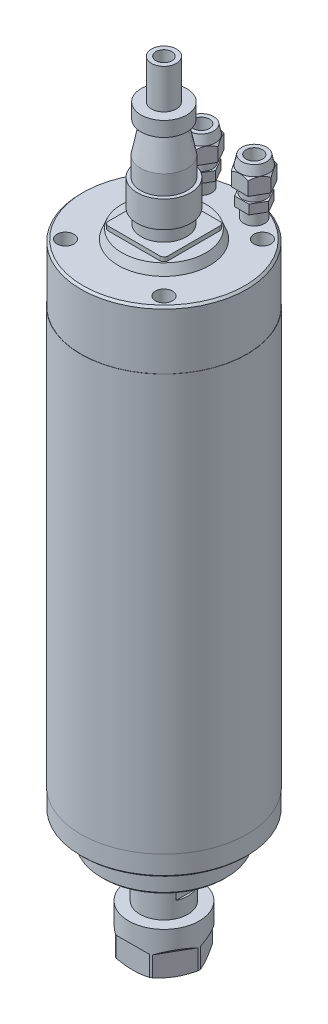
SolidWorks part; units mm, degrees
material "Plain Carbon Steel"
ref_plane "Front Plane" through (0, 0, 0) normal (0, 0, 1) x (1, 0, 0)
ref_plane "Top Plane" through (0, 0, 0) normal (0, 1, 0) x (1, 0, 0)
ref_plane "Right Plane" through (0, 0, 0) normal (1, 0, 0) x (0, 0, -1)
ref_axis "Axis1" through (0, 160.005, 0) along (0, -1, 0)
sketch "Sketch1" plane through (0, 0, 0) normal (1, 0, 0) x (0, 0, -1)
  line L0 (0, 128.3) -> (0, -128.3)
  line L1 (0, 128.3) -> (-39.9, 128.3)
  line L2 (-39.9, 128.3) -> (-39.9, 100.3)
  line L3 (-39.9, 100.3) -> (-40, 100.3)
  line L4 (-40, 100.3) -> (-40, -99.7)
  line L5 (-40, -99.7) -> (-39.9, -99.7)
  line L6 (-39.9, -99.7) -> (-39.9, -109.7)
  line L7 (-39.9, -109.7) -> (-30, -109.7)
  line L8 (-30, -109.7) -> (-30, -123.7)
  line L9 (-30, -123.7) -> (-24.1, -123.7)
  line L10 (-24.1, -123.7) -> (-24.1, -128.3)
  line L11 (-24.1, -128.3) -> (0, -128.3)
  dimension "D1" = 40
  dimension "D2" = 39.9
  dimension "D3" = 39.9
  dimension "D4" = 28
  dimension "D5" = 200
  dimension "D6" = 10
  dimension "D7" = 14
  dimension "D8" = 30
  dimension "D9" = 4.6
  dimension "D10" = 24.1
revolve "Revolve1" add sketch "Sketch1" angle 360 about L0
chamfer "Chamfer2" distance 7 distance2 1.5 1 edges at (0, -128.3, 24.1) first distance on face at (0, -128.3, 24.1)
sketch "Sketch2" plane through (0, -128.3, 0) normal (0, -1, 0) x (1, 0, 0)
  circle A0 centre (0, 0) radius 11.5
  dimension "D1" = 23
extrude "Boss-Extrude1" add sketch "Sketch2" along normal blind 19
chamfer "Chamfer1" distance 1 angle 45 3 edges at (0, 128.3, 39.9) (0, -109.7, 39.9) (0, -123.7, 30)
sketch "Sketch3" plane through (0, -147.3, 0) normal (0, -1, 0) x (1, 0, 0)
  circle A0 centre (0, 0) radius 17
  dimension "D1" = 34
extrude "Boss-Extrude2" add sketch "Sketch3" along normal blind 22.5
ref_plane "Plane1" through (21.67, 0, 0) normal (1, 0, 0) x (0, 0, -1)
chamfer "Chamfer3" distance 2 distance2 4 1 edges at (0, -169.8, -17) first distance on face at (0, -169.8, -17)
sketch "Sketch7" plane through (0, 0, 0) normal (1, 0, 0) x (0, 0, -1)
  line L0 (0, -169.8) -> (0, -147.3) construction
  line L1 (-29.8933, -143.3067) -> (-15, -158.2)
  line L2 (-29.8933, -143.3067) -> (-29.8933, -177.0813)
  line L3 (-29.8933, -177.0813) -> (-15, -177.0813)
  line L4 (-15, -158.2) -> (-15, -177.0813)
  line L5 (-17, -169.8) -> (17, -169.8) construction
  line L6 (17, -147.3) -> (-17, -147.3) construction
  dimension "D1" = 45
  dimension "D2" = 15
  dimension "D3" = 11.6
extrude "Cut-Extrude1" cut sketch "Sketch7" against normal through all both and the other way through all
pattern_circular "CirPattern1" count 6 over 360 about axis through (0, 160.005, 0) along (0, -1, 0) of "Cut-Extrude1"
sketch "Sketch9" plane through (0, -169.8, 0) normal (0, -1, 0) x (1, 0, 0)
  circle A0 centre (0, 0) radius 7.7
  dimension "D1" = 15.4
extrude "Cut-Extrude2" cut sketch "Sketch9" against normal blind 10
sketch "Sketch10" plane through (0, 128.3, 0) normal (0, 1, 0) x (1, 0, 0)
  circle A0 centre (0, 0) radius 22
  dimension "D1" = 44
extrude "Boss-Extrude3" add sketch "Sketch10" along normal blind 4.4 draft 22
sketch "Sketch11" plane through (0, 128.3, 0) normal (0, 1, 0) x (1, 0, 0)
  line L0 (-23.6881, 23.6881) -> (-26.5872, 26.5872) construction
  line L1 (23.6881, -23.6881) -> (-23.6881, -23.6881) construction
  line L2 (23.6881, -23.6881) -> (23.6881, 23.6881) construction
  line L3 (23.6881, 23.6881) -> (-23.6881, 23.6881) construction
  line L4 (-23.6881, -23.6881) -> (-23.6881, 23.6881) construction
  line L5 (23.6881, -23.6881) -> (-23.6881, 23.6881) construction
  line L6 (23.6881, 23.6881) -> (-23.6881, -23.6881) construction
  line L7 (-26.5872, 26.5872) -> (-28.2843, 28.2843) construction
  circle A0 centre (-23.6881, 23.6881) radius 4.1
  circle A1 centre (23.6881, 23.6881) radius 4.1
  circle A2 centre (23.6881, -23.6881) radius 4.1
  circle A3 centre (-23.6881, -23.6881) radius 4.1
  circle A4 centre (0, 0) radius 40 construction
  point P0 (0, 0)
  dimension "D1" = 8.2
  dimension "D2" = 2.4
extrude "Cut-Extrude3" cut sketch "Sketch11" against normal blind 10
sketch "Sketch12" plane through (0, 128.3, 0) normal (0, 1, 0) x (1, 0, 0)
  line L0 (0, 0) -> (0, 30.7) construction
  line L1 (0, 30.7) -> (-12.75, 30.7) construction
  line L2 (-12.75, 30.7) -> (-17.75, 30.7) construction
  circle A0 centre (-12.75, 30.7) radius 5
  dimension "D1" = 10
  dimension "D2" = 17.75
  dimension "D3" = 30.7
extrude "Boss-Extrude4" add sketch "Sketch12" along normal blind 5.8
sketch "Sketch13" plane through (0, 134.1, 0) normal (0, 1, 0) x (1, 0, 0)
  line L1 (-19.6782, 30.7) -> (-16.2141, 24.7)
  line L2 (-16.2141, 24.7) -> (-9.2859, 24.7)
  line L3 (-9.2859, 24.7) -> (-5.8218, 30.7)
  line L4 (-5.8218, 30.7) -> (-9.2859, 36.7)
  line L5 (-9.2859, 36.7) -> (-16.2141, 36.7)
  line L6 (-16.2141, 36.7) -> (-19.6782, 30.7)
  circle A0 centre (-12.75, 30.7) radius 6 construction
  dimension "D1" = 12
extrude "Boss-Extrude5" add sketch "Sketch13" along normal blind 4.5
sketch "Sketch14" plane through (0, 138.6, 0) normal (0, 1, 0) x (1, 0, 0)
  circle A0 centre (-12.75, 30.7) radius 5.5
  dimension "D1" = 11
extrude "Boss-Extrude6" add sketch "Sketch14" along normal blind 4
sketch "Sketch15" plane through (0, 142.6, 0) normal (0, 1, 0) x (1, 0, 0)
  line L1 (-20.8329, 30.7) -> (-16.7915, 23.7)
  line L2 (-16.7915, 23.7) -> (-8.7085, 23.7)
  line L3 (-8.7085, 23.7) -> (-4.6671, 30.7)
  line L4 (-4.6671, 30.7) -> (-8.7085, 37.7)
  line L5 (-8.7085, 37.7) -> (-16.7915, 37.7)
  line L6 (-16.7915, 37.7) -> (-20.8329, 30.7)
  circle A0 centre (-12.75, 30.7) radius 7 construction
  dimension "D1" = 14
extrude "Boss-Extrude7" add sketch "Sketch15" along normal blind 12
ref_axis "Axis2" through (-12.75, 167.8718, -30.7) along (0, -1, 0)
ref_plane "Plane2" through (0, 0, -30.7) normal (0, 0, 1) x (0, -1, 0)
sketch "Sketch16" plane through (0, 0, -30.7) normal (0, 0, 1) x (0, -1, 0)
  line L0 (-154.6, -18.75) -> (-150.2, -19.6777)
  line L1 (-150.2, -19.6777) -> (-142.6099, -27.2678)
  line L2 (-142.6099, -27.2678) -> (-154.6, -27.2678)
  line L3 (-154.6, -27.2678) -> (-154.6, -18.75)
  line L4 (-154.6, -12.75) -> (-154.6, -18.75) construction
  line L5 (-154.6, -16.7915) -> (-154.6, -8.7085) construction
  line L6 (-154.6, -20.8329) -> (-154.6, -16.7915) construction
  dimension "D1" = 6
  dimension "D2" = 4.4
  dimension "D3" = 45
revolve "Cut-Revolve1" cut sketch "Sketch16" angle 360 about axis through (-12.75, 167.8718, -30.7) along (0, -1, 0)
sketch "Sketch17" plane through (0, 154.6, 0) normal (0, 1, 0) x (1, 0, 0)
  circle A0 centre (-12.75, 30.7) radius 3.95
  dimension "D1" = 7.9
extrude "Cut-Extrude4" cut sketch "Sketch17" against normal blind 12
mirror "Mirror1" about plane through (0, 0, 0) normal (1, 0, 0) of "Cut-Extrude4", "Cut-Revolve1", "Boss-Extrude7", "Boss-Extrude6", "Boss-Extrude5", "Boss-Extrude4"
sketch "Sketch18" plane through (0, 132.7, 0) normal (0, 1, 0) x (1, 0, 0)
  line L1 (14.4, 14.4) -> (-14.4, 14.4)
  line L2 (14.4, 14.4) -> (14.4, -14.4)
  line L3 (14.4, -14.4) -> (-14.4, -14.4)
  line L4 (-14.4, 14.4) -> (-14.4, -14.4)
  line L5 (14.4, 14.4) -> (-14.4, -14.4) construction
  line L6 (14.4, -14.4) -> (-14.4, 14.4) construction
  point P0 (0, 0)
  dimension "D1" = 28.8
extrude "Boss-Extrude8" add sketch "Sketch18" along normal blind 2
fillet "Fillet1" radius 2 4 edges at (14.4, 133.7, -14.4) (-14.4, 133.7, -14.4) (14.4, 133.7, 14.4) (-14.4, 133.7, 14.4)
sketch "Sketch19" plane through (0, 0, 0) normal (0, 0, 1) x (1, 0, 0)
  line L0 (0, 0) -> (0, 195.8759) construction
  line L1 (0, 134.7) -> (-10.9, 134.7)
  line L2 (-10.9, 134.7) -> (-10.9, 141.3)
  line L3 (-10.9, 141.3) -> (-12.9, 141.3)
  line L4 (-12.9, 141.3) -> (-12.9, 154.1)
  line L5 (-12.9, 154.1) -> (-11.2, 154.1)
  line L6 (-11.2, 154.1) -> (-11.2, 163.4)
  line L7 (-11.2, 163.4) -> (-8.2, 178.4)
  line L8 (-8.2, 178.4) -> (-11, 178.4)
  line L9 (-11, 178.4) -> (-11, 185.5)
  line L10 (-11, 185.5) -> (-6, 185.5)
  line L11 (0, 185.5) -> (0, 134.7)
  line L12 (-12.4, 134.7) -> (12.4, 134.7) construction
  line L13 (-3.8369, 204.5) -> (-3.8369, 195.8759)
  line L14 (-3.8369, 195.8759) -> (0, 195.8759)
  line L15 (0, 185.5) -> (0, 195.8759)
  line L16 (-3.8369, 204.5) -> (-6, 204.5)
  line L17 (-6, 185.5) -> (-6, 204.5)
  line L18 (0, 204.5) -> (0, 319.5248) construction
  line L19 (0, 204.5) -> (0, 195.8759) construction
  dimension "D1" = 10.9
  dimension "D2" = 6.6
  dimension "D3" = 12.9
  dimension "D4" = 12.8
  dimension "D5" = 11.2
  dimension "D6" = 9.3
  dimension "D7" = 15
  dimension "D8" = 7.1
  dimension "D9" = 11
  dimension "D10" = 8.2
  dimension "D11" = 6
  dimension "D12" = 19
revolve "Revolve2" add sketch "Sketch19" angle 360 about L0
sketch "Sketch20" plane through (0, 0, 0) normal (0, 0, 1) x (1, 0, 0)
  line L0 (0, -128.3) -> (0, -147.3) construction
  line L1 (-11.5, -128.3) -> (11.5, -128.3) construction
  line L2 (17, -147.3) -> (-17, -147.3) construction
  line L3 (10.5, -129.3659) -> (10.5, -139.6659)
  line L4 (-21.6678, -129.3659) -> (-10.5, -129.3659)
  line L5 (-21.6678, -129.3659) -> (-21.6678, -139.6659)
  line L6 (-21.6678, -139.6659) -> (-10.5, -139.6659)
  line L7 (-10.5, -129.3659) -> (-10.5, -139.6659)
  line L8 (21.6678, -139.6659) -> (10.5, -139.6659)
  line L9 (21.6678, -129.3659) -> (21.6678, -139.6659)
  line L10 (21.6678, -129.3659) -> (10.5, -129.3659)
  dimension "D1" = 10.5
  dimension "D2" = 10.3
extrude "Cut-Extrude5" cut sketch "Sketch20" against normal through all both and the other way through all
